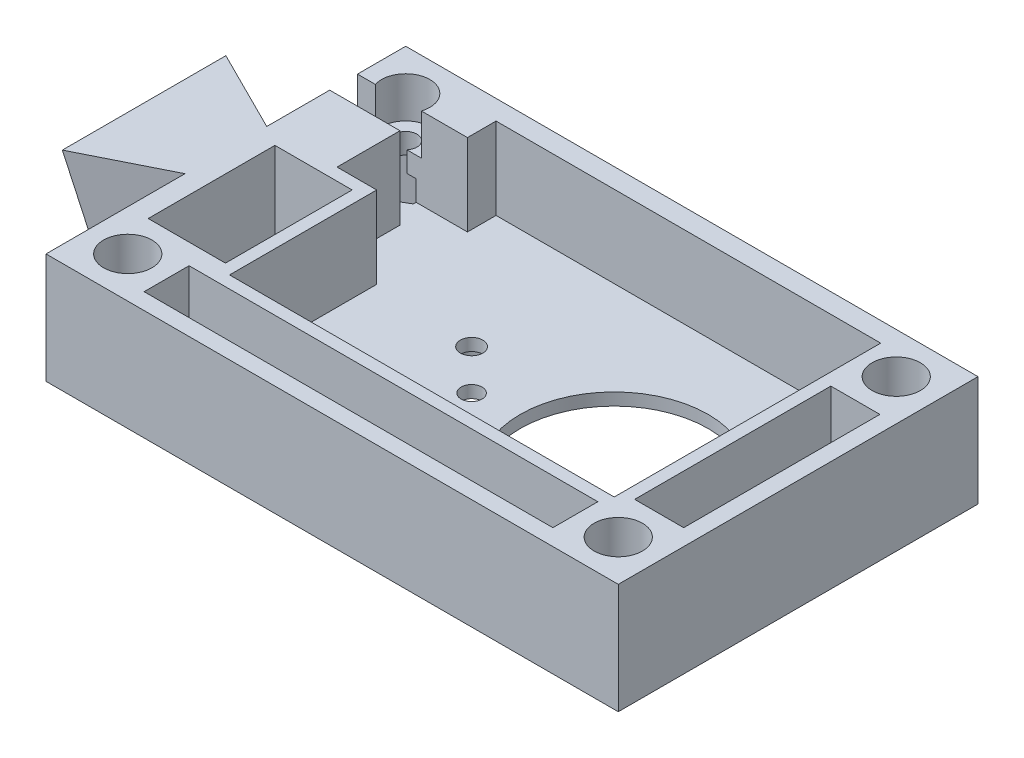
SolidWorks part; units mm, degrees
ref_plane "Front Plane" through (0, 0, 0) normal (0, 0, 1) x (1, 0, 0)
ref_plane "Top Plane" through (0, 0, 0) normal (0, 1, 0) x (1, 0, 0)
ref_plane "Right Plane" through (0, 0, 0) normal (1, 0, 0) x (0, 0, -1)
sketch "Sketch2" plane through (0, 0, 0) normal (0, 1, 0) x (1, 0, 0)
  line L4 (311.785, -2.54) -> (234.315, -2.54)
  line L5 (311.785, -2.54) -> (311.785, 74.93)
  line L6 (311.785, 74.93) -> (234.315, 74.93)
  line L7 (234.315, -2.54) -> (234.315, 74.93)
  line L8 (330.2, -19.685) -> (-50.8, -19.685)
  line L9 (330.2, -19.685) -> (330.2, 92.075)
  line L10 (330.2, 92.075) -> (-50.8, 92.075)
  line L11 (-50.8, -19.685) -> (-50.8, 92.075)
  line L12 (309.88, -0.635) -> (177.8, -0.635)
  line L13 (309.88, -0.635) -> (309.88, 89.789)
  line L14 (309.88, 89.789) -> (177.8, 89.789)
  line L15 (177.8, -0.635) -> (177.8, 89.789)
  line L16 (306.07, 3.175) -> (186.563, 3.175)
  line L17 (306.07, 3.175) -> (306.07, 85.979)
  line L18 (306.07, 85.979) -> (186.563, 85.979)
  line L19 (186.563, 3.175) -> (186.563, 85.979)
  line L20 (186.563, 48.895) -> (174.244, 48.895)
  line L21 (186.563, 48.895) -> (186.563, 77.089)
  line L22 (186.563, 77.089) -> (174.244, 77.089)
  line L23 (174.244, 48.895) -> (174.244, 77.089)
  line L24 (174.244, 68.453) -> (167.64, 68.453)
  line L25 (174.244, 68.453) -> (174.244, 77.089)
  line L26 (174.244, 77.089) -> (167.64, 77.089)
  line L27 (167.64, 68.453) -> (167.64, 77.089)
  line L28 (152.4, 92.075) -> (152.4, -19.685)
  line L33 (152.4, 48.895) -> (127, 61.595)
  line L34 (127, 61.595) -> (127, 10.795)
  line L35 (127, 10.795) -> (152.4, 23.495)
  circle A0 centre (273.05, 36.195) radius 20.32
  circle A1 centre (273.05, 36.195) radius 29.21
  dimension "D1" = 40.64
  dimension "D2" = 58.42
  dimension "D3" = 82.804
  dimension "D4" = 90.424
  dimension "D5" = 132.08
  dimension "D6" = 119.507
  dimension "D7" = 3.81
  dimension "D8" = 3.81
  dimension "D9" = 28.194
  dimension "D10" = 8.636
  dimension "D11" = 12.319
  dimension "D12" = 381
  dimension "D13" = 33.02
  dimension "D14" = 33.02
  dimension "D15" = 111.76
  dimension "D16" = 77.47
  dimension "D17" = 57.15
  dimension "D18" = 38.735
  dimension "D19" = 77.47
  dimension "D20" = 38.735
  dimension "D21" = 50.8
  dimension "D22" = 8.89
  dimension "D23" = 55.88
  dimension "D24" = 12.7
  dimension "D25" = 25.4
  dimension "D26" = 12.7
  dimension "D27" = 25.4
  dimension "D28" = 177.8
sketch "Sketch3" plane through (0, 0, 0) normal (0, 1, 0) x (1, 0, 0)
  line L1 (-50.8, 92.075) -> (330.2, 92.075)
  line L2 (-50.8, 92.075) -> (-50.8, -19.685)
  line L3 (-50.8, -19.685) -> (330.2, -19.685)
  line L4 (330.2, 92.075) -> (330.2, -19.685)
extrude "Boss-Extrude1" add sketch "Sketch3" along normal blind 34.29
extrude "Cut-Extrude2" cut sketch "Sketch2<4>" along normal blind 127 contours A1
sketch "Sketch2<4>" plane through (0, 0, 0) normal (0, 1, 0) x (1, 0, 0) same geometry as "Sketch2"
extrude "Cut-Extrude3" cut sketch "Sketch2<5>" along normal blind 127 from offset 8.89 contours L16 L19 L18 L17
sketch "Sketch2<5>" plane through (0, 0, 0) normal (0, 1, 0) x (1, 0, 0) same geometry as "Sketch2"
extrude "Cut-Extrude4" cut sketch "Sketch2" along normal blind 127 from surface contours L22 L21 L20 L23 | L25 L24 L27 L26 starting at face at (273.05, 8.89, -6.985)
sketch "Sketch4" plane through (0, 34.29, 0) normal (0, 1, 0) x (1, 0, 0)
  line L0 (152.4, 48.895) -> (127, 61.595)
  line L1 (127, 61.595) -> (127, 10.795)
  line L2 (127, 10.795) -> (152.4, 23.495)
  line L3 (152.4, 23.495) -> (152.4, -19.685)
  line L4 (152.4, -19.685) -> (-50.8, -19.685)
  line L5 (-50.8, -19.685) -> (-50.8, 92.075)
  line L6 (-50.8, 92.075) -> (152.4, 92.075)
  line L7 (152.4, 92.075) -> (152.4, 48.895)
extrude "Cut-Extrude6" cut sketch "Sketch4" against normal blind 127
sketch "Sketch6" plane through (0, 0, 19.685) normal (0, 0, 1) x (1, 0, 0)
  line L0 (127, 34.29) -> (136.188, 0)
  line L1 (152.4, 0) -> (127, 0) construction
  line L2 (136.188, 0) -> (101.0547, 0)
  line L3 (330.2, 0) -> (-50.8, 0) construction
  line L4 (101.0547, 0) -> (127, 34.29)
  line L5 (127, 0) -> (127, 34.29) construction
  dimension "D1" = 15
extrude "Cut-Extrude7" cut sketch "Sketch6" against normal blind 127
sketch "Sketch7" plane through (0, 34.29, 0) normal (0, 1, 0) x (1, 0, 0)
  line L1 (167.64, 77.089) -> (147.9501, 77.089)
  line L2 (167.64, 77.089) -> (167.64, 68.453)
  line L3 (167.64, 68.453) -> (147.9501, 68.453)
  line L4 (147.9501, 77.089) -> (147.9501, 68.453)
extrude "Cut-Extrude8" cut sketch "Sketch7" against normal up to surface (25.4 mm away) up to face at (273.05, 8.89, -6.985)
sketch "Sketch8" plane through (0, 0, 0) normal (0, -1, 0) x (1, 0, 0)
  line L1 (221.996, -87.249) -> (324.104, -87.249)
  line L2 (221.996, -87.249) -> (221.996, 14.859)
  line L3 (221.996, 14.859) -> (324.104, 14.859)
  line L4 (324.104, -87.249) -> (324.104, 14.859)
  line L5 (221.996, -87.249) -> (324.104, 14.859) construction
  line L6 (221.996, 14.859) -> (324.104, -87.249) construction
  point P0 (273.05, -36.195)
  dimension "D1" = 102.108
  dimension "D2" = 102.108
extrude "Cut-Extrude9" cut sketch "Sketch8" against normal blind 5.08
sketch "Sketch9" plane through (0, 34.29, 0) normal (0, 1, 0) x (1, 0, 0)
  line L0 (330.2, -19.685) -> (330.2, 92.075) construction
  line L1 (165.1, 79.375) -> (317.5, 79.375)
  line L2 (165.1, 79.375) -> (165.1, -6.985)
  line L3 (165.1, -6.985) -> (317.5, -6.985)
  line L4 (317.5, 79.375) -> (317.5, -6.985)
  line L5 (330.2, 92.075) -> (152.4, 92.075) construction
  line L6 (152.4, 77.089) -> (152.4, 92.075) construction
  line L7 (152.4, -19.685) -> (330.2, -19.685) construction
  line L8 (152.4, 92.075) -> (330.2, 92.075)
  line L9 (330.2, 92.075) -> (330.2, -19.685)
  line L10 (330.2, -19.685) -> (152.4, -19.685)
  line L11 (152.4, -19.685) -> (152.4, 23.495)
  line L12 (152.4, 23.495) -> (127, 10.795)
  line L13 (127, 10.795) -> (127, 61.595)
  line L14 (127, 61.595) -> (152.4, 48.895)
  line L15 (152.4, 48.895) -> (152.4, 92.075)
  circle A0 centre (317.5, 79.375) radius 7.5
  circle A1 centre (317.5, -6.985) radius 7.5
  circle A3 centre (165.1, 79.375) radius 7.5
  circle A4 centre (165.1, -6.985) radius 7.5
  dimension "D1" = 15
  dimension "D2" = 15
  dimension "D3" = 15
  dimension "D4" = 15
  dimension "D5" = 12.7
  dimension "D6" = 12.7
  dimension "D7" = 12.7
  dimension "D8" = 12.7
extrude "Cut-Extrude10" cut sketch "Sketch9" against normal blind 12.7 contours A0 | A1 | A4 | A3
sketch "Sketch10" plane through (0, 21.59, 0) normal (0, 1, 0) x (1, 0, 0)
  circle A0 centre (317.5, 79.375) radius 3.5
  circle A1 centre (317.5, -6.985) radius 3.5
  circle A2 centre (165.1, -6.985) radius 3.5
  circle A3 centre (165.1, 79.375) radius 3.5
  dimension "D1" = 7
  dimension "D2" = 7
  dimension "D3" = 7
  dimension "D4" = 7
extrude "Cut-Extrude11" cut sketch "Sketch10" against normal blind 55.372
sketch "Sketch11" plane through (0, 0, 0) normal (0, -1, 0) x (1, 0, 0)
  line L1 (159.6, -82.5504) -> (165.1, -85.7259)
  line L2 (165.1, -85.7259) -> (170.6, -82.5504)
  line L3 (170.6, -82.5504) -> (170.6, -76.1996)
  line L4 (170.6, -76.1996) -> (165.1, -73.0241)
  line L5 (165.1, -73.0241) -> (159.6, -76.1996)
  line L6 (159.6, -76.1996) -> (159.6, -82.5504)
  line L7 (312, 3.8096) -> (317.5, 0.6341)
  line L8 (317.5, 0.6341) -> (323, 3.8096)
  line L9 (323, 3.8096) -> (323, 10.1604)
  line L10 (323, 10.1604) -> (317.5, 13.3359)
  line L11 (317.5, 13.3359) -> (312, 10.1604)
  line L12 (312, 10.1604) -> (312, 3.8096)
  line L13 (165.1, 0.6341) -> (170.6, 3.8096)
  line L14 (170.6, 3.8096) -> (170.6, 10.1604)
  line L15 (170.6, 10.1604) -> (165.1, 13.3359)
  line L16 (165.1, 13.3359) -> (159.6, 10.1604)
  line L17 (159.6, 10.1604) -> (159.6, 3.8096)
  line L18 (159.6, 3.8096) -> (165.1, 0.6341)
  line L19 (317.5, -85.7259) -> (323, -82.5504)
  line L20 (323, -82.5504) -> (323, -76.1996)
  line L21 (323, -76.1996) -> (317.5, -73.0241)
  line L22 (317.5, -73.0241) -> (312, -76.1996)
  line L23 (312, -76.1996) -> (312, -82.5504)
  line L24 (312, -82.5504) -> (317.5, -85.7259)
  circle A0 centre (165.1, -79.375) radius 5.5 construction
  circle A1 centre (317.5, 6.985) radius 5.5 construction
  circle A2 centre (165.1, 6.985) radius 5.5 construction
  circle A3 centre (317.5, -79.375) radius 5.5 construction
  dimension "D1" = 11
  dimension "D2" = 11
  dimension "D3" = 11
  dimension "D4" = 11
extrude "Cut-Extrude12" cut sketch "Sketch11" against normal blind 15.24
sketch "Sketch12" plane through (0, 8.89, 0) normal (0, 1, 0) x (1, 0, 0)
  circle A0 centre (230.55, 34.395) radius 3.25
  circle A1 centre (218.05, 46.895) radius 3.5
extrude "Cut-Extrude13" cut sketch "Sketch12" against normal blind 12.446
sketch "Sketch13" plane through (0, 0, 0) normal (0, -1, 0) x (1, 0, 0)
  circle A0 centre (218.05, -46.895) radius 7.5
  dimension "D1" = 15
extrude "Cut-Extrude14" cut sketch "Sketch13" against normal up to surface (5.08 mm away) up to face at (230.55, 5.08, -31.145)
sketch "Sketch14" plane through (0, 34.29, 0) normal (0, 1, 0) x (1, 0, 0)
  line L0 (152.4, -19.685) -> (330.2, -19.685) construction
  line L1 (304.8, -14.605) -> (177.8, -14.605)
  line L2 (304.8, -14.605) -> (304.8, -0.635)
  line L3 (304.8, -0.635) -> (177.8, -0.635)
  line L4 (177.8, -14.605) -> (177.8, -0.635)
  line L5 (186.563, 3.175) -> (306.07, 3.175) construction
  line L6 (330.2, -19.685) -> (330.2, 92.075) construction
  line L7 (152.4, -19.685) -> (152.4, 23.495) construction
  line L8 (330.2, 92.075) -> (152.4, 92.075) construction
  line L9 (182.753, 5.715) -> (158.75, 5.715)
  line L10 (182.753, 5.715) -> (182.753, 45.085)
  line L11 (182.753, 45.085) -> (158.75, 45.085)
  line L12 (158.75, 5.715) -> (158.75, 45.085)
  line L13 (325.12, 5.715) -> (309.88, 5.715)
  line L14 (325.12, 5.715) -> (325.12, 66.675)
  line L15 (325.12, 66.675) -> (309.88, 66.675)
  line L16 (309.88, 5.715) -> (309.88, 66.675)
  line L17 (186.563, 48.895) -> (186.563, 3.175) construction
  line L18 (174.244, 48.895) -> (186.563, 48.895) construction
  line L19 (306.07, 85.979) -> (306.07, 3.175) construction
  dimension "D1" = 5.08
  dimension "D2" = 3.81
  dimension "D3" = 25.4
  dimension "D4" = 25.4
  dimension "D5" = 25.4
  dimension "D6" = 25.4
  dimension "D7" = 25.4
  dimension "D8" = 3.81
  dimension "D9" = 6.35
  dimension "D10" = 3.81
  dimension "D11" = 5.08
  dimension "D12" = 3.81
extrude "Cut-Extrude15" cut sketch "Sketch14" against normal blind 25.4
